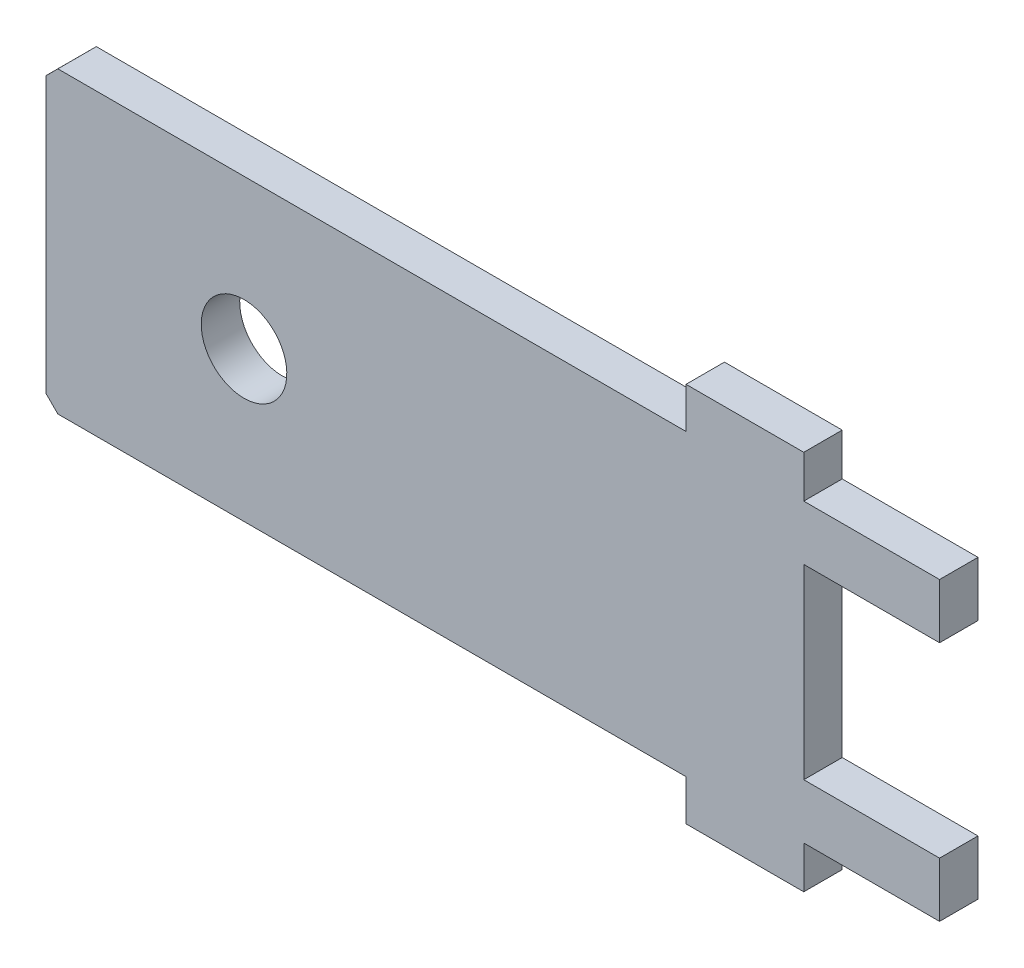
SolidWorks part; units mm, degrees
ref_plane "Plan de face" through (0, 0, 0) normal (0, 0, 1) x (1, 0, 0)
ref_plane "Plan de dessus" through (0, 0, 0) normal (0, 1, 0) x (1, 0, 0)
ref_plane "Plan de droite" through (0, 0, 0) normal (1, 0, 0) x (0, 0, -1)
sketch "Esquisse1" plane through (0, 0, 0) normal (0, 0, 1) x (0, 1, 0)
  line L0 (-3.96, 0.034) -> (-3.08, 0.034)
  line L1 (1.94, 0.034) -> (1.94, -2.7911)
  line L2 (3.08, 0.034) -> (3.08, -2.7911)
  line L3 (2.4644, 16.2) -> (-2.4644, 16.2)
  line L4 (3.96, 0.034) -> (3.96, 2.484)
  line L5 (3.96, 2.484) -> (3.11, 2.484)
  line L6 (3.11, 2.484) -> (3.11, 15.5532)
  line L7 (3.08, -2.7911) -> (1.94, -2.7911)
  line L9 (-2.4644, 16.2) -> (-3.11, 15.5532)
  line L10 (-3.08, -2.7911) -> (-1.94, -2.7911)
  line L11 (-3.11, 2.484) -> (-3.11, 15.5532)
  line L12 (-3.96, 2.484) -> (-3.11, 2.484)
  line L13 (-3.96, 0.034) -> (-3.96, 2.484)
  line L14 (-3.08, 0.034) -> (-3.08, -2.7911)
  line L15 (2.4644, 16.2) -> (3.11, 15.5532)
  line L16 (-1.94, 0.034) -> (-1.94, -2.7911)
  line L17 (-1.94, 0.034) -> (1.94, 0.034)
  line L18 (3.08, 0.034) -> (3.96, 0.034)
  point P18 (0, 0.034)
  point P25 (0, 0.034)
  dimension "D1" = 13.716
  dimension "D2" = 2.45
  dimension "D3" = 1.94
  dimension "D4" = 3.96
  dimension "D5" = 0.85
  dimension "D6" = 1.14
extrude "Extrusion1" add sketch "Esquisse1" along normal blind 0.8
sketch "Esquisse2" plane through (0, 0, 0.8) normal (0, 0, 1) x (0, 1, 0)
  line L0 (2.4644, 16.2) -> (-2.4644, 16.2) construction
  circle A0 centre (0, 11.68) radius 0.89
  dimension "D1" = 4.52
extrude "Enlèv. mat.-Extru.1" cut sketch "Esquisse2" against normal blind 0.8
chamfer "Chanfrein1" distance 0.4 angle 45 1 edges at (-16.2, 0, 0)
chamfer "Chanfrein2" distance 0.4 angle 45 1 edges at (-16.2, 0, 0.8)
